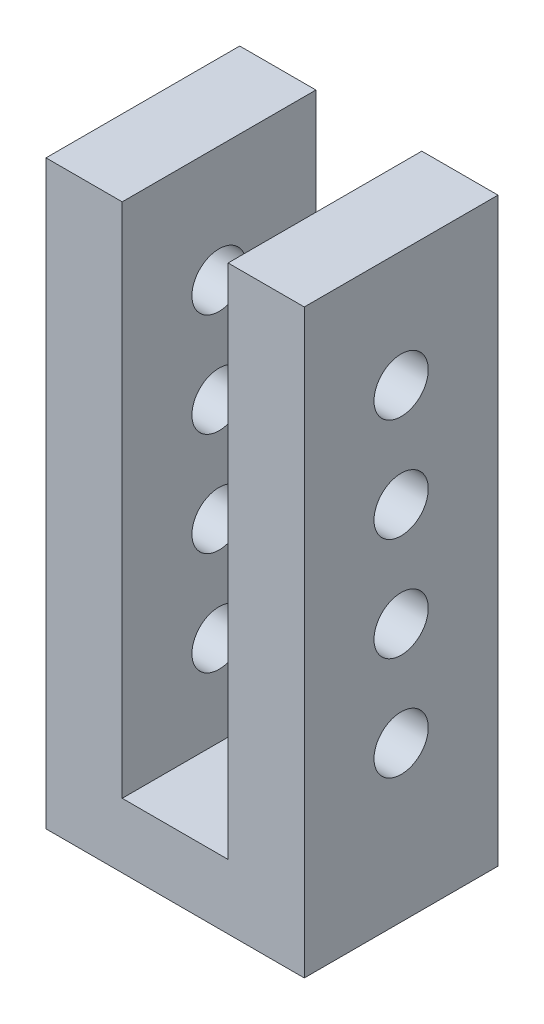
SolidWorks part; units mm, degrees
ref_plane "Спереди" through (0, 0, 0) normal (0, 0, 1) x (1, 0, 0)
ref_plane "Сверху" through (0, 0, 0) normal (0, 1, 0) x (1, 0, 0)
ref_plane "Справа" through (0, 0, 0) normal (1, 0, 0) x (0, 0, -1)
sketch "Эскиз5" plane through (0, 0, 0) normal (0, 1, 0) x (1, 0, 0)
  line L1 (0, 0) -> (20, 0)
  line L2 (0, 0) -> (0, 15)
  line L3 (0, 15) -> (20, 15)
  line L4 (20, 0) -> (20, 15)
  dimension "D1" = 15
  dimension "D2" = 20
extrude "Вытянуть5" add sketch "Эскиз5" along normal blind 5
sketch "Эскиз6" plane through (0, 5, 0) normal (0, 1, 0) x (1, 0, 0)
  line L0 (0, 7.5) -> (20, 7.5) construction
  line L1 (0, 15) -> (0, 0) construction
  line L2 (20, 0) -> (20, 15) construction
  circle A0 centre (10, 7.5) radius 2.1
  dimension "D1" = 4.2
extrude "Вытянуть6" cut sketch "Эскиз6" against normal up to next
sketch "Эскиз7" plane through (0, 5, 0) normal (0, 1, 0) x (1, 0, 0)
  line L0 (0, 0) -> (20, 0) construction
  line L1 (0, 15) -> (5.9, 15)
  line L2 (0, 15) -> (0, 0)
  line L3 (0, 0) -> (5.9, 0)
  line L4 (5.9, 15) -> (5.9, 0)
  line L6 (20, 15) -> (14.1, 15)
  line L7 (20, 15) -> (20, 0)
  line L8 (20, 0) -> (14.1, 0)
  line L9 (14.1, 15) -> (14.1, 0)
  dimension "D1" = 8.2
extrude "Вытянуть7" add sketch "Эскиз7" along normal blind 40
sketch "Эскиз8" plane through (0, 0, 0) normal (-1, 0, 0) x (0, 0, 1)
  line L0 (0, 0) -> (-15, 0) construction
  line L1 (0, 45) -> (0, 0) construction
  circle A0 centre (-7.5, 20) radius 2.1
  circle A1 centre (-7.5, 28) radius 2.1
  circle A2 centre (-7.5, 12) radius 2.1
  circle A3 centre (-7.5, 36) radius 2.1
  point P14 (0, 0)
  dimension "D1" = 4.2
  dimension "D2" = 20
  dimension "D3" = 7.5
  dimension "D4" = 8
  dimension "D5" = 8
  dimension "D6" = 8
extrude "Вытянуть8" cut sketch "Эскиз8" against normal through all
